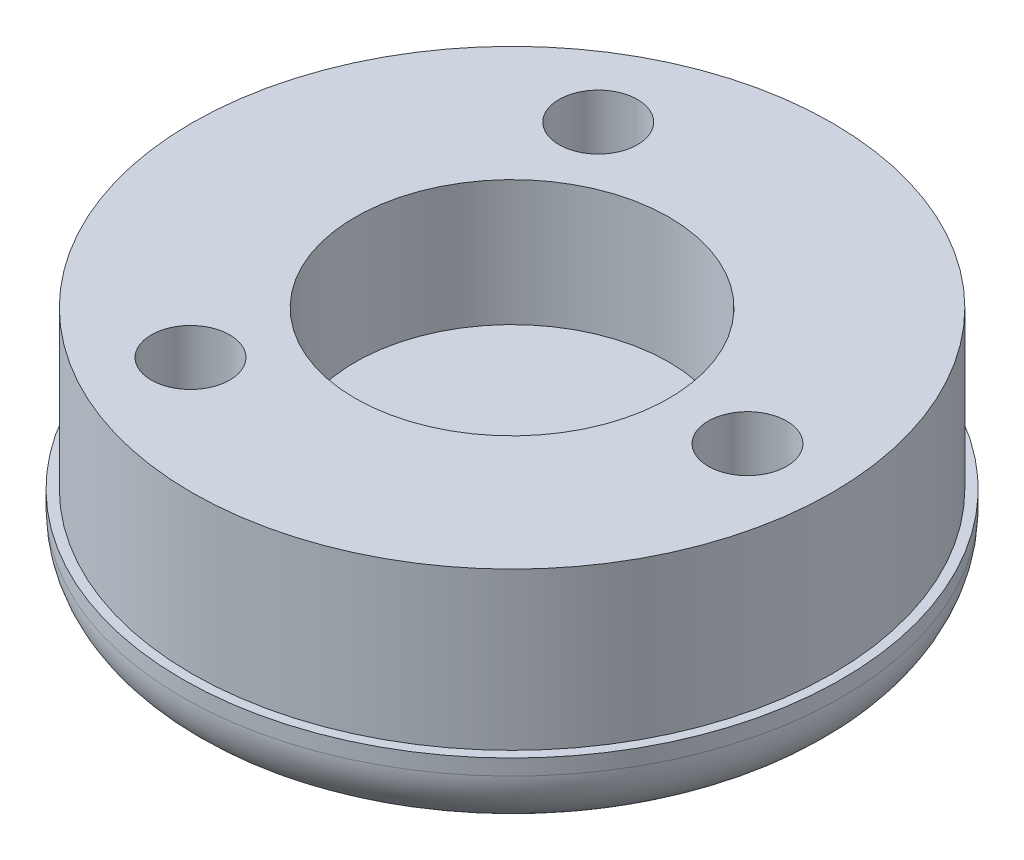
SolidWorks part; units mm, degrees
ref_plane "Front Plane" through (0, 0, 0) normal (0, 0, 1) x (1, 0, 0)
ref_plane "Top Plane" through (0, 0, 0) normal (0, 1, 0) x (1, 0, 0)
ref_plane "Right Plane" through (0, 0, 0) normal (1, 0, 0) x (0, 0, -1)
sketch "Sketch1" plane through (0, 0, 0) normal (0, 1, 0) x (1, 0, 0)
  circle A0 centre (0, 0) radius 13.335
extrude "Boss-Extrude1" add sketch "Sketch1" along normal blind 3.175 contours A0
sketch "Sketch2" plane through (0, 3.175, 0) normal (0, 1, 0) x (1, 0, 0)
  circle A0 centre (0, 0) radius 12.954
extrude "Boss-Extrude2" add sketch "Sketch2" along normal blind 6.35
sketch "Sketch3" plane through (0, 9.525, 0) normal (0, 1, 0) x (1, 0, 0)
  circle A0 centre (0, 0) radius 6.35
extrude "Cut-Extrude2" cut sketch "Sketch3" against normal blind 5.08
sketch "Sketch4" plane through (0, 9.525, 0) normal (0, 1, 0) x (1, 0, 0)
  circle A1 centre (9.525, 0) radius 1.5875
extrude "Cut-Extrude3" cut sketch "Sketch4" against normal blind 2.54 contours A1
ref_axis "Axis1" through (0, 4.445, 0) along (0, 1, 0)
pattern_circular "CirPattern1" count 3 every 120 about axis through (0, 4.445, 0) along (0, 1, 0) of "Cut-Extrude3"
fillet "Fillet1" radius 2.54 1 edges at (0, 0, 13.335)
sketch "Sketch5" plane through (0, 0, 0) normal (0, -1, 0) x (1, 0, 0)
  circle A0 centre (0, 0) radius 22.86
  circle A1 centre (0, 0) radius 12.7
